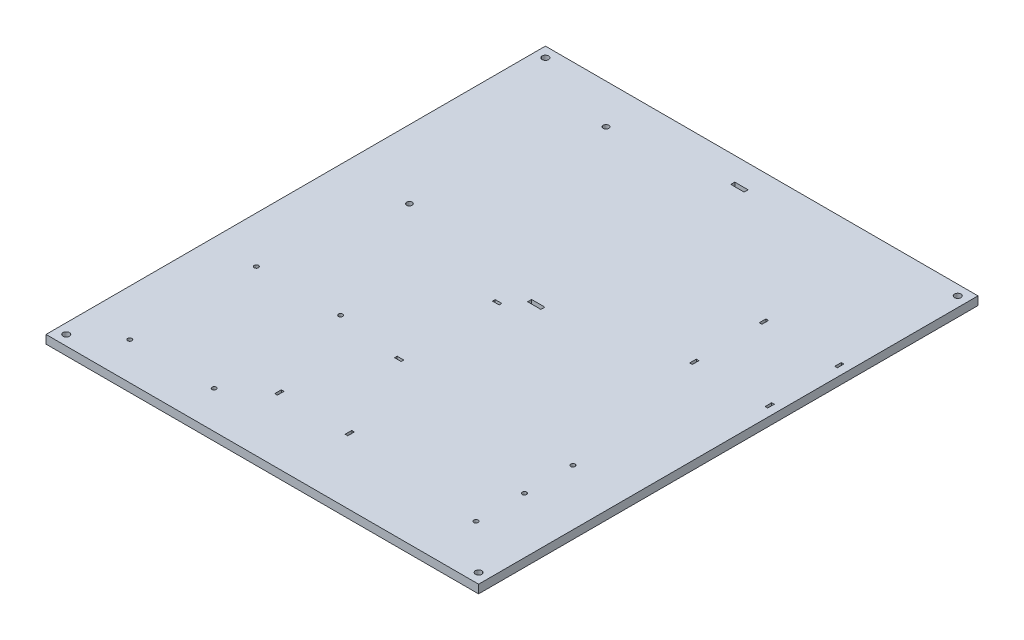
SolidWorks part; units mm, degrees
ref_plane "Front Plane" through (0, 0, 0) normal (0, 0, 1) x (1, 0, 0)
ref_plane "Top Plane" through (0, 0, 0) normal (0, 1, 0) x (1, 0, 0)
ref_plane "Right Plane" through (0, 0, 0) normal (1, 0, 0) x (0, 0, -1)
sketch "Sketch1" plane through (0, 0, 0) normal (0, 1, 0) x (1, 0, 0)
  line L0 (31.75, 126.6) -> (31.75, 25) construction
  line L1 (0, 376) -> (325.7, 376)
  line L2 (0, 376) -> (0, 0)
  line L3 (0, 0) -> (325.7, 0)
  line L4 (325.7, 376) -> (325.7, 0)
  line L5 (25.4, 350.6) -> (110.9, 350.6) construction
  line L6 (25.4, 350.6) -> (25.4, 217.6) construction
  line L7 (25.4, 217.6) -> (110.9, 217.6) construction
  line L8 (110.9, 350.6) -> (110.9, 217.6) construction
  line L9 (25.4, 126.6) -> (101.6, 126.6) construction
  line L10 (25.4, 126.6) -> (25.4, 25) construction
  line L11 (25.4, 25) -> (101.6, 25) construction
  line L12 (101.6, 126.6) -> (101.6, 25) construction
  line L13 (264.9, 278.5813) -> (315.7, 278.5813) construction
  line L14 (135, 350.6) -> (249.5, 350.6) construction
  line L15 (135, 350.6) -> (135, 210.6) construction
  line L16 (135, 210.6) -> (249.5, 210.6) construction
  line L17 (249.5, 350.6) -> (249.5, 210.6) construction
  line L18 (165, 350.6) -> (165, 210.6) construction
  line L19 (271.7, 123) -> (295.7, 123) construction
  line L20 (271.7, 123) -> (271.7, 30) construction
  line L21 (271.7, 30) -> (295.7, 30) construction
  line L22 (295.7, 123) -> (295.7, 30) construction
  line L23 (264.9, 304.775) -> (315.7, 304.775) construction
  line L24 (264.9, 304.775) -> (264.9, 200) construction
  line L25 (264.9, 200) -> (315.7, 200) construction
  line L26 (315.7, 304.775) -> (315.7, 200) construction
  line L27 (160, 205.6) -> (170, 205.6)
  line L28 (160, 358.6) -> (170, 358.6)
  line L29 (160, 358.6) -> (160, 355.6)
  line L30 (160, 355.6) -> (170, 355.6)
  line L31 (170, 358.6) -> (170, 355.6)
  line L32 (160, 205.6) -> (160, 202.6)
  line L33 (160, 202.6) -> (170, 202.6)
  line L34 (170, 205.6) -> (170, 202.6)
  line L35 (148.88, 187.8) -> (148.88, 120) construction
  line L36 (113.88, 187.8) -> (180.38, 187.8) construction
  line L37 (113.88, 187.8) -> (113.88, 120) construction
  line L38 (113.88, 120) -> (180.38, 120) construction
  line L39 (180.38, 187.8) -> (180.38, 120) construction
  line L40 (146.38, 191.8) -> (151.38, 191.8)
  line L41 (146.38, 118) -> (151.38, 118)
  line L42 (146.38, 118) -> (146.38, 116)
  line L43 (146.38, 116) -> (151.38, 116)
  line L44 (151.38, 118) -> (151.38, 116)
  line L45 (146.38, 191.8) -> (146.38, 189.8)
  line L46 (146.38, 189.8) -> (151.38, 189.8)
  line L47 (151.38, 191.8) -> (151.38, 189.8)
  line L48 (128.7, 50) -> (175.7, 50) construction
  line L49 (128.7, 82) -> (175.7, 82) construction
  line L50 (128.7, 82) -> (128.7, 35) construction
  line L51 (128.7, 35) -> (175.7, 35) construction
  line L52 (175.7, 82) -> (175.7, 35) construction
  line L53 (124.7, 52.5) -> (126.7, 52.5)
  line L54 (177.7, 52.5) -> (179.7, 52.5)
  line L55 (177.7, 52.5) -> (177.7, 47.5)
  line L56 (177.7, 47.5) -> (179.7, 47.5)
  line L57 (179.7, 52.5) -> (179.7, 47.5)
  line L58 (124.7, 52.5) -> (124.7, 47.5)
  line L59 (124.7, 47.5) -> (126.7, 47.5)
  line L60 (126.7, 52.5) -> (126.7, 47.5)
  line L61 (264.9, 226.1937) -> (315.7, 226.1937) construction
  line L62 (317.7, 228.6937) -> (319.7, 228.6937)
  line L63 (317.7, 228.6937) -> (317.7, 223.6937)
  line L64 (317.7, 223.6937) -> (319.7, 223.6937)
  line L65 (319.7, 228.6937) -> (319.7, 223.6937)
  line L66 (260.9, 228.6937) -> (262.9, 228.6937)
  line L67 (260.9, 228.6937) -> (260.9, 223.6937)
  line L68 (260.9, 223.6937) -> (262.9, 223.6938)
  line L69 (262.9, 228.6937) -> (262.9, 223.6938)
  line L70 (317.7, 281.0813) -> (319.7, 281.0813)
  line L71 (317.7, 281.0813) -> (317.7, 276.0813)
  line L72 (317.7, 276.0813) -> (319.7, 276.0813)
  line L73 (319.7, 281.0813) -> (319.7, 276.0813)
  line L74 (260.9, 281.0813) -> (262.9, 281.0813)
  line L75 (260.9, 281.0813) -> (260.9, 276.0813)
  line L76 (260.9, 276.0813) -> (262.9, 276.0813)
  line L77 (262.9, 281.0813) -> (262.9, 276.0813)
  circle A0 centre (7.62, 368.38) radius 2.413
  circle A1 centre (75.438, 346.1828) radius 2.0828
  circle A2 centre (51.562, 222.0172) radius 2.0828
  circle A3 centre (318.08, 368.38) radius 2.413
  circle A4 centre (7.62, 7.62) radius 2.413
  circle A5 centre (318.08, 7.62) radius 2.413
  circle A6 centre (34.925, 123.425) radius 1.5875
  circle A7 centre (98.425, 123.425) radius 1.5875
  circle A8 centre (34.925, 28.1751) radius 1.5875
  circle A9 centre (98.425, 28.1751) radius 1.5875
  circle A10 centre (283.7, 113) radius 1.6256
  circle A11 centre (283.7, 40) radius 1.6256
  circle A12 centre (283.7, 76.5) radius 1.6256
  point P49 (283.7, 30)
  point P50 (283.7, 123)
  point P58 (165, 355.6)
  point P64 (165, 205.6)
  point P75 (148.88, 118)
  point P81 (148.88, 189.8)
  point P92 (177.7, 50)
  point P98 (126.7, 50)
  point P107 (317.7, 226.1937)
  point P113 (262.9, 226.1937)
  point P118 (317.7, 278.5813)
  point P124 (262.9, 278.5813)
  dimension "D9" = 4.826
  dimension "D13" = 4.1656
  dimension "D14" = 4.1656
  dimension "D16" = 310.46
  dimension "D22" = 3.175
  dimension "D25" = 63.5
  dimension "D37" = 200
  dimension "D51" = 3.2512
  dimension "D62" = 26.1937
  dimension "D1" = 376
  dimension "D2" = 325.7
  dimension "D3" = 25.4
  dimension "D4" = 25.4
  dimension "D5" = 133
  dimension "D6" = 85.5
  dimension "D7" = 7.62
  dimension "D8" = 7.62
  dimension "D10" = 50.038
  dimension "D11" = 26.162
  dimension "D12" = 4.4172
  dimension "D15" = 4.4172
  dimension "D17" = 360.76
  dimension "D18" = 101.6
  dimension "D19" = 76.2
  dimension "D20" = 25.4
  dimension "D21" = 25
  dimension "D23" = 3.175
  dimension "D24" = 3.175
  dimension "D26" = 95.2499
  dimension "D27" = 6.35
  dimension "D28" = 114.5
  dimension "D29" = 140
  dimension "D30" = 25.4
  dimension "D31" = 76.2
  dimension "D32" = 24
  dimension "D33" = 30
  dimension "D34" = 93
  dimension "D35" = 30
  dimension "D36" = 30
  dimension "D38" = 10
  dimension "D39" = 10
  dimension "D40" = 10
  dimension "D41" = 3
  dimension "D42" = 5
  dimension "D43" = 10
  dimension "D44" = 3
  dimension "D45" = 5
  dimension "D46" = 66.5
  dimension "D47" = 67.8
  dimension "D48" = 145.32
  dimension "D49" = 120
  dimension "D50" = 35
  dimension "D52" = 46.5
  dimension "D53" = 2
  dimension "D54" = 2
  dimension "D55" = 5
  dimension "D56" = 2
  dimension "D57" = 47
  dimension "D58" = 47
  dimension "D59" = 15
  dimension "D60" = 150
  dimension "D61" = 35
  dimension "D63" = 50.8
  dimension "D64" = 2
  dimension "D65" = 104.775
  dimension "D66" = 26.1937
  dimension "D67" = 2
  dimension "D69" = 10
  dimension "D70" = 2
  dimension "D71" = 2
  dimension "D72" = 2
  dimension "D73" = 2
extrude "Extrude1" add sketch "Sketch1" along normal blind 6.35
